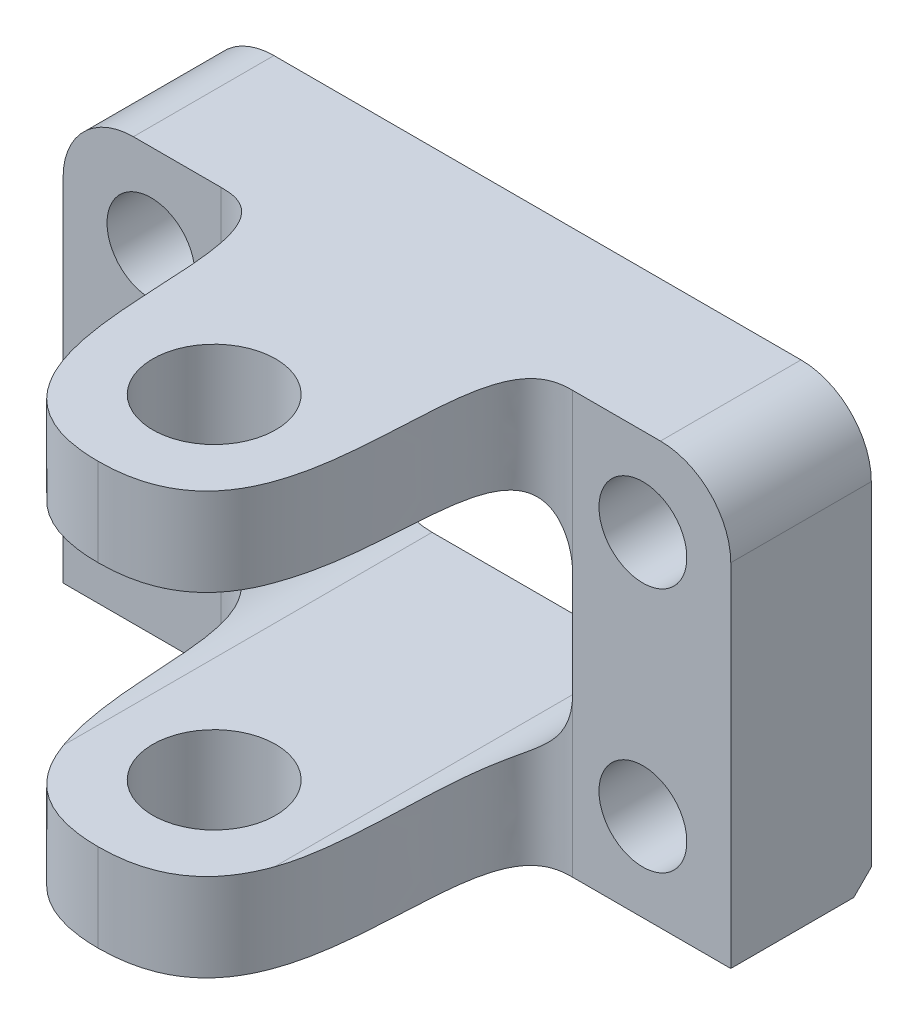
SolidWorks part; units mm, degrees
material "6061-T6 (SS)"
ref_plane "Front Plane" through (0, 0, 0) normal (0, 0, 1) x (1, 0, 0)
ref_plane "Top Plane" through (0, 0, 0) normal (0, 1, 0) x (1, 0, 0)
ref_plane "Right Plane" through (0, 0, 0) normal (1, 0, 0) x (0, 0, -1)
sketch "Sketch1" plane through (0, 0, 0) normal (0, 1, 0) x (1, 0, 0)
  line L0 (0, 29.21) -> (0, 0) construction
  line L1 (30.1625, -10.4775) -> (-30.1625, -10.4775) construction
  line L2 (30.1625, -10.4775) -> (30.1625, 29.21) construction
  line L3 (30.1625, 29.21) -> (-30.1625, 29.21)
  line L4 (-30.1625, -10.4775) -> (-30.1625, 29.21) construction
  line L5 (-30.1625, 16.51) -> (-15.875, 16.51)
  line L6 (-38.0288, 16.51) -> (-47.6787, 16.51) construction
  line L7 (-33.4659, -10.4775) -> (-55.4343, -10.4775) construction
  line L8 (30.1625, 16.51) -> (15.875, 16.51)
  line L9 (-30.1625, 29.21) -> (-30.1625, 16.51)
  line L10 (30.1625, 29.21) -> (30.1625, 16.51)
  circle A0 centre (0, 0) radius 5.5562
  spline S0 degree 3 poles (-15.875, 16.51) (-15.3804, 16.51) (-6.3583, 15.7395) (-16.8885, -10.4775) (0, -10.4775) knots 0 0 0 0 0.05 1 1 1 1
  spline S1 degree 3 poles (15.875, 16.51) (15.3804, 16.51) (6.3583, 15.7395) (16.8885, -10.4775) (0, -10.4775) knots 0 0 0 0 0.05 1 1 1 1
  dimension "D3" = 11.1125
  dimension "D1" = 60.325
  dimension "D2" = 39.6875
  dimension "D4" = 29.21
  dimension "D5" = 31.75
  dimension "D7" = 12.7
extrude "Boss-Extrude2" add sketch "Sketch1" along normal mid plane 38.1
sketch "Sketch2" plane through (0, 0, -29.21) normal (0, 0, 1) x (1, 0, 0)
  line L1 (-15.875, 11.1125) -> (15.875, 11.1125)
  line L2 (-15.875, 11.1125) -> (-15.875, -11.1125)
  line L3 (-15.875, -11.1125) -> (15.875, -11.1125)
  line L4 (15.875, 11.1125) -> (15.875, -11.1125)
  line L7 (30.1625, 0) -> (-30.1625, 0) construction
  line L8 (30.1625, 19.05) -> (30.1625, -19.05) construction
  line L9 (-30.1625, 19.05) -> (-30.1625, -19.05) construction
  line L10 (0, 0) -> (0, 27.954) construction
  dimension "D1" = 31.75
  dimension "D2" = 22.225
extrude "Cut-Extrude1" cut sketch "Sketch2" along normal through all
sketch "Sketch3" plane through (0, 0, -29.21) normal (0, 0, 1) x (1, 0, 0)
  line L4 (30.1625, 0) -> (-30.1625, 0) construction
  line L5 (0, 0) -> (0, 19.05) construction
  line L6 (-30.1625, 19.05) -> (-30.1625, -19.05) construction
  line L8 (15.875, 19.05) -> (0, 19.05) construction
  circle A0 centre (-22.225, 11.1125) radius 3.9688
  circle A1 centre (22.225, 11.1125) radius 3.9688
  circle A2 centre (-22.225, -11.1125) radius 3.9688
  circle A3 centre (22.225, -11.1125) radius 3.9688
  dimension "D9" = 7.9375
  dimension "D1" = 22.225
  dimension "D2" = 11.1125
extrude "Cut-Extrude2" cut sketch "Sketch3" along normal through all
sketch "Sketch4" plane through (0, 0, 0) normal (0, 1, 0) x (1, 0, 0)
  circle A0 centre (0, 0) radius 5.5562 construction
  circle A1 centre (0, 0) radius 5.5562
fillet "Fillet1" radius 6.35 4 edges at (15.875, 11.1125, -22.86) (15.875, -11.1125, -22.86) (-15.875, -11.1125, -22.86) (-15.875, 11.1125, -22.86)
sketch "Sketch5" plane through (0, 0, -16.51) normal (0, 0, 1) x (1, 0, 0)
  line L1 (-29.5138, 10.3145) -> (-25.1783, 4.4012)
  line L2 (-25.1783, 4.4012) -> (-17.8895, 5.1992)
  line L3 (-17.8895, 5.1992) -> (-14.9362, 11.9105)
  line L4 (-14.9362, 11.9105) -> (-19.2717, 17.8238)
  line L5 (-19.2717, 17.8238) -> (-26.5605, 17.0258)
  line L6 (-26.5605, 17.0258) -> (-29.5138, 10.3145)
  circle A0 centre (-22.225, 11.1125) radius 7.3323 construction
  dimension "D1" = 12.7
fillet "Fillet2" radius 6.35 2 edges at (30.1625, 19.05, -22.86) (-30.1625, 19.05, -22.86)
chamfer "Chamfer1" distance 1.5875 angle 45 1 edges at (0, -19.05, -29.21)
